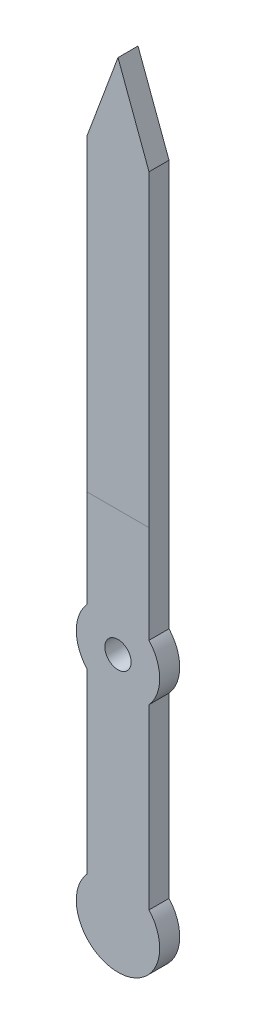
SolidWorks part; units mm, degrees
material "Acrylic (Medium-high impact)"
ref_plane "Front Plane" through (0, 0, 0) normal (0, 0, 1) x (1, 0, 0)
ref_plane "Top Plane" through (0, 0, 0) normal (0, 1, 0) x (1, 0, 0)
ref_plane "Right Plane" through (0, 0, 0) normal (1, 0, 0) x (0, 0, -1)
sketch "Sketch1" plane through (0, 0, 0) normal (0, 0, 1) x (1, 0, 0)
  line L0 (0, 0) -> (0, 19.685) construction
  line L1 (0, 0) -> (0, -8.89) construction
  line L3 (-1.1811, -1.0607) -> (-1.1811, -7.8293)
  line L4 (1.1811, -1.0607) -> (1.1811, -7.8293)
  line L5 (-1.1811, 0) -> (-1.1811, -8.89) construction
  line L6 (1.1811, 0) -> (1.1811, -8.89) construction
  line L7 (1.1811, 1.0607) -> (1.1811, 16.51)
  line L8 (-1.1811, 1.0607) -> (-1.1811, 16.51)
  line L9 (-1.1811, 0) -> (-1.1811, 19.685) construction
  line L10 (1.1811, 0) -> (1.1811, 19.685) construction
  line L11 (0, 19.685) -> (-1.1811, 16.51)
  line L12 (0, 19.685) -> (1.1811, 16.51)
  circle A0 centre (0, 0) radius 0.5
  arc A1 (1.1811, -1.0607) -> (1.1811, 1.0607) centre (0, 0) ccw
  arc A2 (-1.1811, -7.8293) -> (1.1811, -7.8293) centre (0, -8.89) ccw
  arc A3 (-1.1811, 1.0607) -> (-1.1811, -1.0607) centre (0, 0) ccw
  dimension "D1" = 1
  dimension "D2" = 3.175
  dimension "D5" = 1.1811
  dimension "D3" = 19.685
  dimension "D4" = 8.89
  dimension "D9" = 3.175
  dimension "D6" = 1.1811
  dimension "D8" = 1.1811
extrude "Boss-Extrude1" add sketch "Sketch1" along normal blind 0.762
sketch "Sketch2" plane through (0, 0, 0.762) normal (0, 0, 1) x (1, 0, 0)
  line L0 (-1.1811, 4.7752) -> (1.1811, 4.7752)
  line L1 (-1.1811, 16.51) -> (-1.1811, 1.0607) construction
  line L2 (1.1811, 1.0607) -> (1.1811, 16.51) construction
  dimension "D1" = 4.7752
split line "Split Line1"
